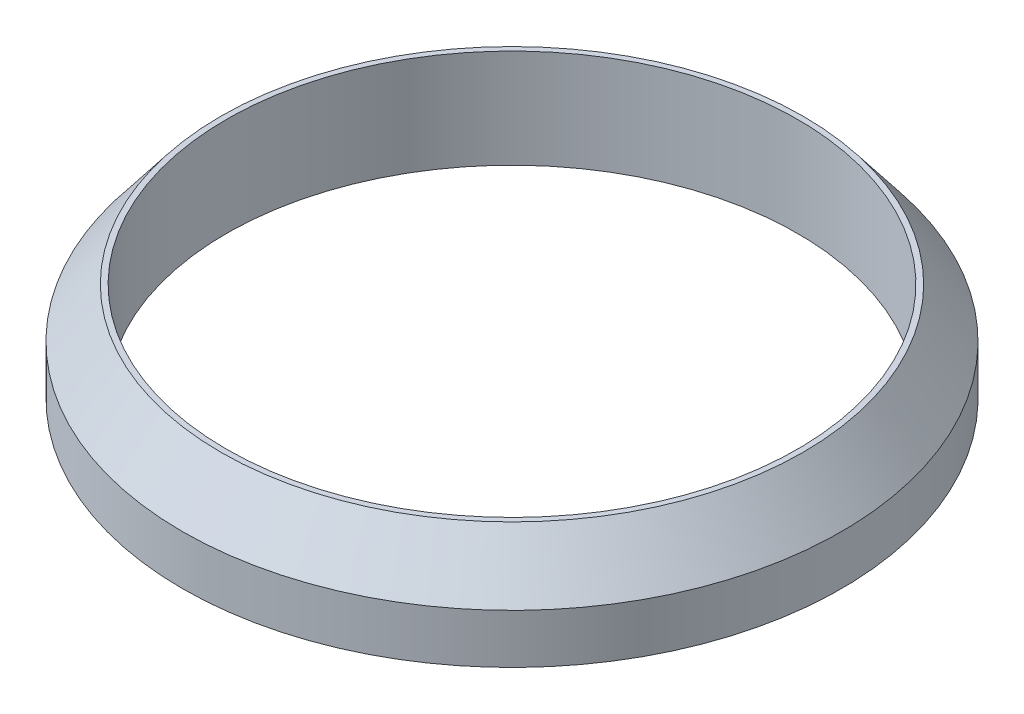
SolidWorks part; units mm, degrees
ref_plane "Front Plane" through (0, 0, 0) normal (0, 0, 1) x (1, 0, 0)
ref_plane "Top Plane" through (0, 0, 0) normal (0, 1, 0) x (1, 0, 0)
ref_plane "Right Plane" through (0, 0, 0) normal (1, 0, 0) x (0, 0, -1)
sketch "Sketch2" plane through (0, 0, 0) normal (0, 1, 0) x (1, 0, 0)
  circle A0 centre (0, 0) radius 76.2
  circle A1 centre (0, 0) radius 66.04
  dimension "D1" = 152.4
  dimension "D2" = 132.08
extrude "Boss-Extrude1" add sketch "Sketch2" along normal blind 22.86
sketch "Sketch5" plane through (0, 0, 0) normal (1, 0, 0) x (0, 0, -1)
  line L4 (0, 0) -> (0, 50000) construction
  line L5 (-76.2, 11.43) -> (-67.31, 22.86)
  line L6 (-76.2, 22.86) -> (-76.2, 0) construction
  line L7 (76.2, 22.86) -> (-76.2, 22.86) construction
  line L8 (-67.31, 22.86) -> (-76.2, 22.86)
  line L9 (-76.2, 22.86) -> (-76.2, 11.43)
  dimension "D1" = 67.31
revolve "Cut-Revolve2" cut sketch "Sketch5" angle 360 about L4
